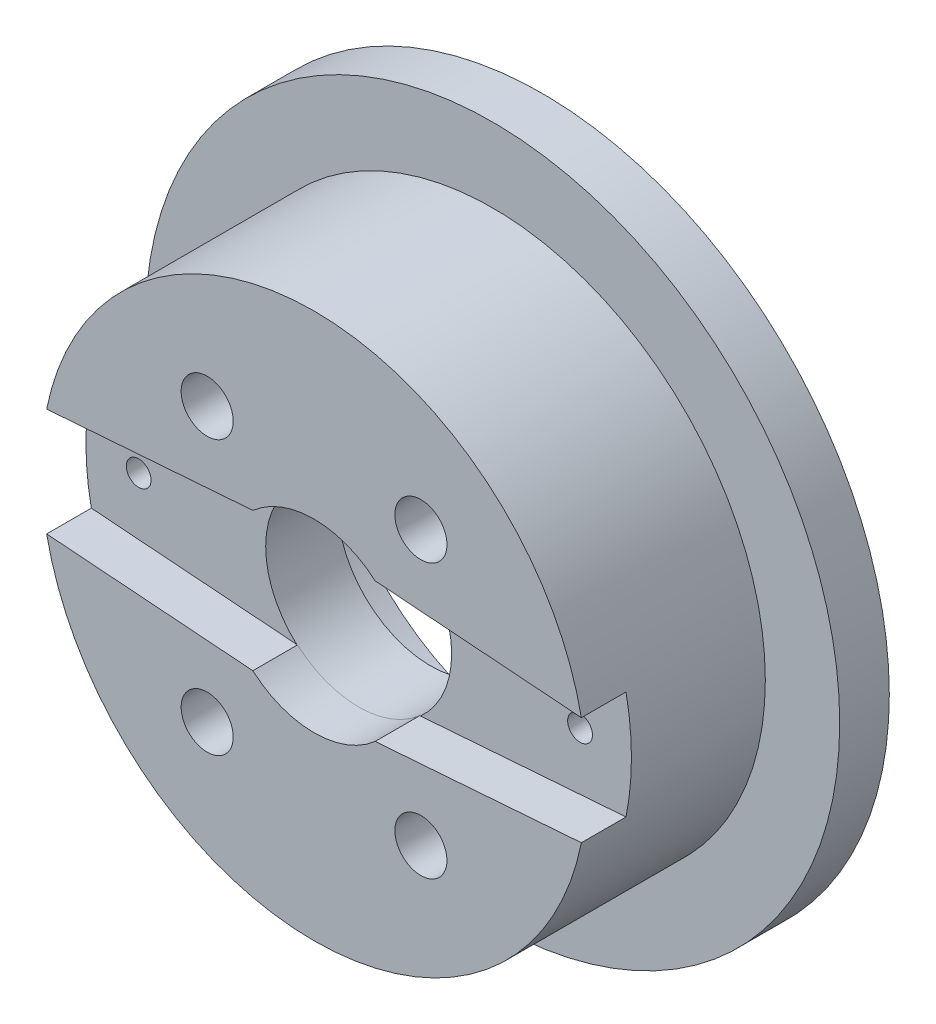
SolidWorks part; units mm, degrees
material "ABS"
ref_plane "Front" through (0, 0, 0) normal (0, 0, 1) x (1, 0, 0)
ref_plane "Top" through (0, 0, 0) normal (0, 1, 0) x (1, 0, 0)
ref_plane "Right" through (0, 0, 0) normal (1, 0, 0) x (0, 0, -1)
sketch "Esquisse1" plane through (0, 0, 0) normal (0, 1, 0) x (1, 0, 0)
  line L8 (0, 0) -> (0, 19.1122) construction
  line L16 (-11, 0) -> (-3.75, 0)
  line L17 (-11, 5.4) -> (-11, 0)
  line L18 (-14, 5.4) -> (-11, 5.4)
  line L19 (-14, 7.4) -> (-14, 5.4)
  line L20 (-9, 7.4) -> (-14, 7.4)
  line L21 (-9, 2.9) -> (-9, 7.4)
  line L22 (-3.75, 2.9) -> (-9, 2.9)
  line L23 (-3.75, 0) -> (-3.75, 2.9)
  dimension "D1" = 2
  dimension "D2" = 2.9
  dimension "D3" = 2
  dimension "D4" = 7.5
  dimension "D5" = 18
  dimension "D6" = 4.5
  dimension "D7" = 3
revolve "Révolution1" add sketch "Esquisse1" angle 360 about L8
ref_axis "Axe1" through (0, 0, -2) along (0, 0, 1)
sketch "Esquisse2" plane through (0, 0, 0) normal (0, 0, 1) x (1, 0, 0)
  line L0 (-8.8726, 0) -> (8.9274, 0) construction
  line L1 (0, 0) -> (0, 18.8109) construction
  line L8 (-2.4683, 2.8) -> (-10.782, 2.1793)
  line L9 (-10.782, -2.1793) -> (-2.4683, -2.8)
  line L10 (2.4633, -2.8045) -> (10.7811, -2.1834)
  line L11 (10.7811, 2.1834) -> (2.4633, 2.8045)
  circle A0 centre (0, 0) radius 11 construction
  arc A1 (-10.782, -2.1793) -> (10.7811, -2.1834) centre (0, 0) ccw
  arc A2 (10.7811, 2.1834) -> (-10.782, 2.1793) centre (0, 0) ccw
  arc A4 (-2.4683, -2.8) -> (2.4633, -2.8045) centre (0, 0) ccw
  arc A5 (2.4633, 2.8045) -> (-2.4683, 2.8) centre (0, 0) ccw
  circle A6 centre (-8.8726, 0) radius 0.5
  circle A7 centre (8.9274, 0) radius 0.5
  dimension "D3" = 3.7326
  dimension "D4" = 1
  dimension "D5" = 1
  dimension "D1" = 5.6
  dimension "D2" = 5.6089
  dimension "D6" = 17.8
  dimension "D7" = 8.9274
  dimension "D8" = 2.1793
  dimension "D9" = 2.1834
extrude "Boss.-Extru.1" add sketch "Esquisse2" along normal blind 1.8
sketch "Esquisse4" plane through (0, 0, 1.8) normal (0, 0, 1) x (1, 0, 0)
  circle A0 centre (-8.8726, 0) radius 0.5 construction
  circle A1 centre (8.9274, 0) radius 0.5 construction
  circle A2 centre (-8.8726, 0) radius 0.5
  circle A3 centre (8.9274, 0) radius 0.5
extrude "Enlèv. mat.-Extru.3" cut sketch "Esquisse4" against normal through all
sketch "Esquisse6" plane through (0, 0, -2.9) normal (0, 0, -1) x (-1, 0, 0)
  line L0 (-8.9274, 0) -> (8.8726, 0) construction
  line L1 (0, 0) -> (0, 6.5657) construction
  line L2 (0, 0) -> (-4.3096, 5.5161) construction
  circle A0 centre (-4.3096, 5.5161) radius 2.1
  circle A1 centre (4.3096, 5.5161) radius 2.1
  circle A2 centre (-4.3096, -5.5161) radius 2.1
  circle A3 centre (4.3096, -5.5161) radius 2.1
  dimension "D1" = 4.2
  dimension "D2" = 7
  dimension "D3" = 38
extrude "Enlèv. mat.-Extru.4" cut sketch "Esquisse6" against normal blind 2
sketch "Esquisse7" plane through (0, 0, -2.9) normal (0, 0, -1) x (-1, 0, 0)
  circle A2 centre (4.3096, -5.5161) radius 1.05
  circle A4 centre (-4.3096, -5.5161) radius 1.05
  circle A6 centre (4.3096, 5.5161) radius 1.05
  circle A8 centre (-4.3096, 5.5161) radius 1.05
  dimension "D1" = 2.1
  dimension "D2" = 2.1
  dimension "D3" = 2.1
  dimension "D4" = 2.1
extrude "Enlèv. mat.-Extru.5" cut sketch "Esquisse7" against normal through all
